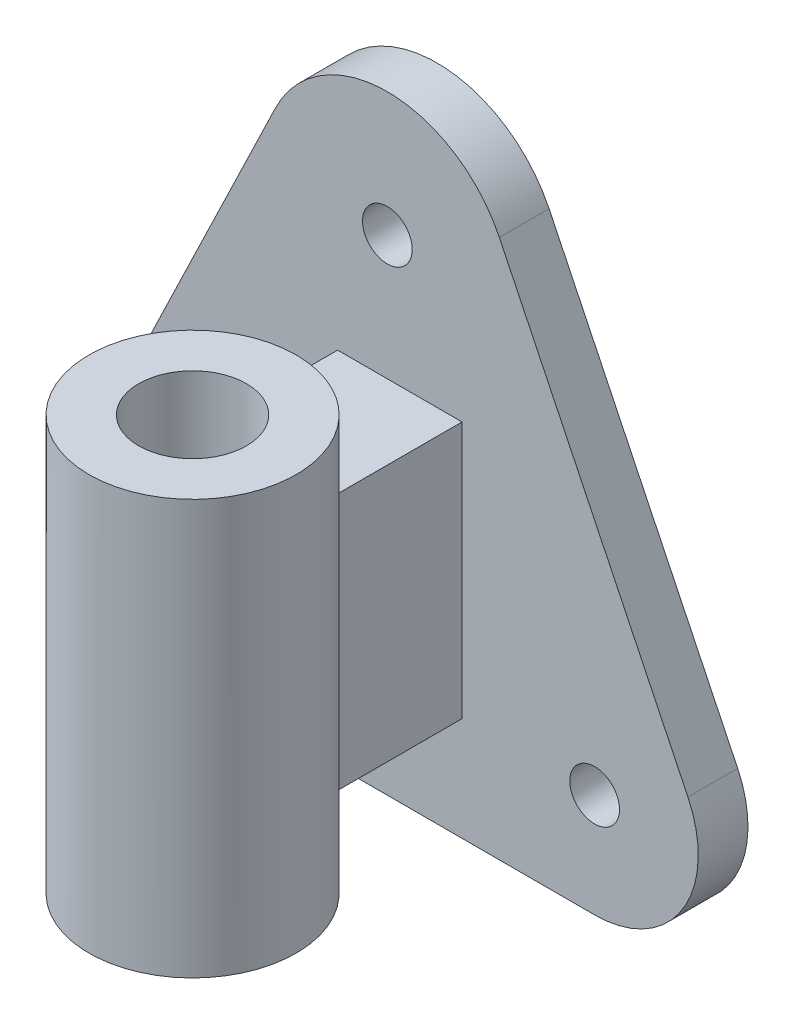
SolidWorks part; units mm, degrees
note: The reader was unsure of these and kept them because the rebuilt part matched: shared geometry of "Çizim4<6>".
ref_plane "Ön Düzlem" through (0, 0, 0) normal (0, 0, 1) x (1, 0, 0)
ref_plane "Üst Düzlem" through (0, 0, 0) normal (0, 1, 0) x (1, 0, 0)
ref_plane "Sağ Düzlem" through (0, 0, 0) normal (1, 0, 0) x (0, 0, -1)
sketch "Çizim2" plane through (0, 0, 0) normal (0, 0, 1) x (1, 0, 0)
  line L0 (17.3321, 35.8753) -> (62.83, 130.0504)
  line L1 (39.8427, 0) -> (139.8427, 0)
  line L5 (116.8554, 130.0504) -> (162.3533, 35.8753)
  arc A0 (139.8427, 0) -> (162.3533, 35.8753) centre (139.8427, 25) ccw
  arc A1 (39.8427, 0) -> (17.3321, 35.8753) centre (39.8427, 25) cw
  arc A2 (116.8554, 130.0504) -> (62.83, 130.0504) centre (89.8427, 117) ccw
  circle A3 centre (89.8427, 117) radius 6
  circle A4 centre (39.8427, 25) radius 6
  circle A5 centre (139.8427, 25) radius 6
  point P8 (0, 0)
  point P11 (89.8427, 147)
  point P12 (89.8427, 0)
  dimension "D1" = 25
  dimension "D2" = 30
  dimension "D5" = 12
  dimension "D3" = 100
  dimension "D4" = 92
extrude "Yükseklik-Ekstrüzyon2" add sketch "Çizim2" along normal blind 12
ref_plane "Düzlem1" through (0, 25, 0) normal (0, -1, 0) x (-1, 0, 0)
sketch "Çizim4" plane through (0, 25, 0) normal (0, -1, 0) x (-1, 0, 0)
  line L0 (-39.8427, -12) -> (-139.8427, -12) construction
  line L2 (-77.8514, -42) -> (-77.8514, -12)
  line L3 (-77.8514, -12) -> (-107.8514, -12)
  line L4 (-107.8514, -42) -> (-107.8514, -12)
  circle A0 centre (-92.8514, -62) radius 25
  circle A1 centre (-92.8514, -62) radius 13
  point P6 (-89.8427, -12)
  dimension "D3" = 50
  dimension "D4" = 26
  dimension "D5" = 15
  dimension "D1" = 30
  dimension "D2" = 50
extrude "Yükseklik-Ekstrüzyon3" add sketch "Çizim4" against normal blind 62 contours A0 L2 L3 L4 | A0 A1 | A1
extrude "Yükseklik-Ekstrüzyon4" add sketch "Çizim4<6>" along normal blind 19 contours A1 | A0
sketch "Çizim4<6>" plane through (0, 25, 0) normal (0, -1, 0) x (-1, 0, 0) same geometry as "Çizim4"
sketch "Çizim5" plane through (0, 87, 0) normal (0, 1, 0) x (1, 0, 0)
  circle A0 centre (92.8514, -62) radius 13
  circle A1 centre (92.8514, -62) radius 25
extrude "Yükseklik-Ekstrüzyon5" add sketch "Çizim5" along normal blind 19
